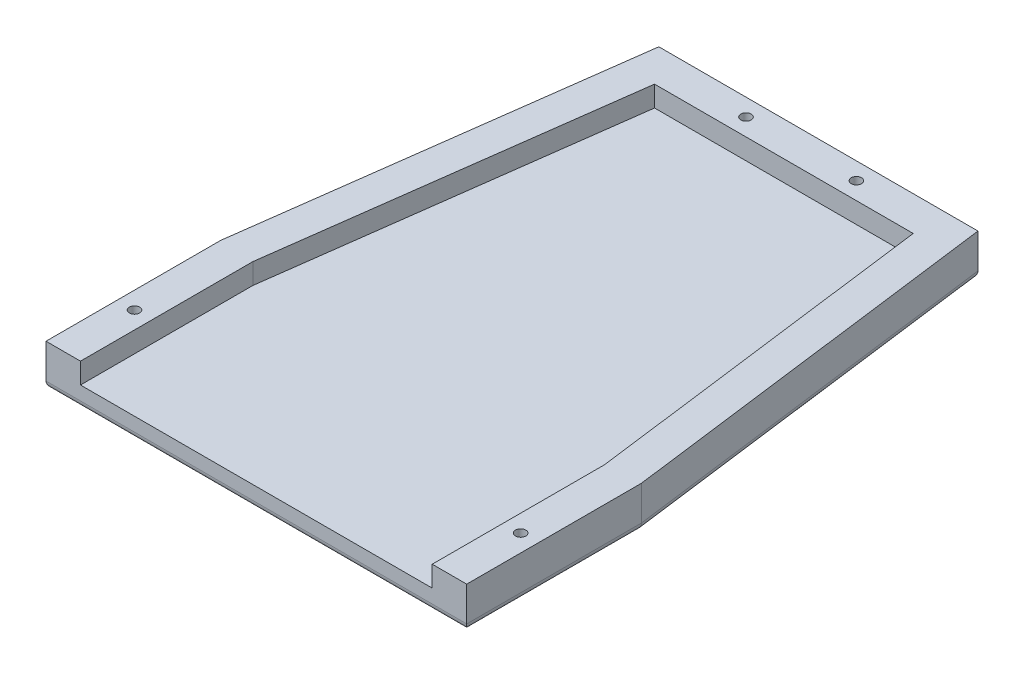
SolidWorks part; units mm, degrees
ref_plane "Płaszczyzna przednia" through (0, 0, 0) normal (0, 0, 1) x (1, 0, 0)
ref_plane "Płaszczyzna górna" through (0, 0, 0) normal (0, 1, 0) x (1, 0, 0)
ref_plane "Płaszczyzna prawa" through (0, 0, 0) normal (1, 0, 0) x (0, 0, -1)
sketch "Szkic1" plane through (0, 0, 0) normal (0, 1, 0) x (1, 0, 0)
  line L0 (-46.2252, 44.9878) -> (-0.2252, 44.9878)
  line L1 (-0.2252, 44.9878) -> (7.2748, -12.8855)
  line L2 (7.2748, -12.8855) -> (7.2748, -36.4122)
  line L3 (7.2748, -36.4122) -> (-53.7252, -36.4122)
  line L4 (-53.7252, -36.4122) -> (-53.7252, -11.4122)
  line L5 (-53.7252, -11.4122) -> (-46.2252, 44.9878)
  dimension "D1" = 46
  dimension "D2" = 61
  dimension "D3" = 7.5
  dimension "D4" = 56.4
  dimension "D5" = 25
  dimension "D6" = 7.5
extrude "Dodanie-wyciągnięcie1" add sketch "Szkic1" along normal blind 3
sketch "Szkic3" plane through (0, 0, 0) normal (0, 1, 0) x (1, 0, 0)
  line L0 (-48.7252, -31.4122) -> (2.2748, -31.4122)
  line L1 (-53.7252, -11.4122) -> (-53.7252, -36.4122) construction
  line L2 (7.2748, -36.4122) -> (7.2748, -12.8855) construction
  line L3 (-48.7252, -31.4122) -> (-48.7252, -11.4122)
  line L4 (-53.7252, -36.4122) -> (7.2748, -36.4122) construction
  line L5 (-41.8901, 39.9878) -> (-4.3863, 39.9878)
  line L6 (-0.2252, 44.9878) -> (-46.2252, 44.9878) construction
  line L7 (-4.3863, 39.9878) -> (2.2748, -11.4122)
  line L8 (-48.7252, -11.4122) -> (-41.8901, 39.9878)
  line L9 (2.2748, -31.4122) -> (2.2748, -11.4122)
  line L10 (-46.2252, 44.9878) -> (-53.7252, -11.4122) construction
  line L11 (7.2748, -12.8855) -> (-0.2252, 44.9878) construction
  dimension "D1" = 51
  dimension "D2" = 5
  dimension "D3" = 5
  dimension "D4" = 5
  dimension "D5" = 20
  dimension "D6" = 5
  dimension "D7" = 0
  dimension "D8" = 0
  dimension "D9" = 20
extrude "Wyciągnięcie-cienka ścianka1" add sketch "Szkic3" along normal blind 6 from offset 0 thin contours L7 L9 L0 L3 L8 L5 thin type one direction wall 5
sketch "Szkic5" plane through (0, 6, 0) normal (0, 1, 0) x (1, 0, 0)
  line L0 (-46.2692, 44.9878) -> (0.0075, 44.9878) construction
  line L1 (7.2748, -36.4122) -> (7.2748, -11.0896) construction
  line L2 (-53.7252, -36.4122) -> (-53.7252, -11.0812) construction
  circle A0 centre (-31.1292, 42.4878) radius 0.75
  circle A1 centre (-15.1292, 42.4878) radius 0.75
  circle A2 centre (-51.2252, -26.0812) radius 0.75
  circle A3 centre (4.7748, -26.0896) radius 0.75
  dimension "D3" = 1.5
  dimension "D4" = 1.5
  dimension "D8" = 1.5
  dimension "D9" = 1.5
  dimension "D1" = 2.5
  dimension "D2" = 2.5
  dimension "D5" = 16
  dimension "D6" = 15.14
  dimension "D7" = 15.1368
  dimension "D10" = 2.5
  dimension "D11" = 2.5
  dimension "D12" = 15
  dimension "D13" = 15
  dimension "D14" = 10.7609
  dimension "D15" = 10.7429
extrude "Wytnij-wyciągnięcie1" cut sketch "Szkic5" against normal blind 39 and the other way blind 51
fillet "Zaokrąglenie1" radius 1 10 edges at (-23.1308, 0, -44.9878) (-49.9972, 0, -16.9533) (-53.7252, 0, 23.7467) (-23.2252, 0, 36.4122) (7.2748, 0, 23.7509) (3.6412, 0, -16.9491) (-31.1292, 0, -43.2378) (-15.1292, 0, -43.2378) (4.7748, 0, 25.3396) (-51.2252, 0, 25.3312)
sketch "Szkic6" plane through (0, 6, 0) normal (0, 1, 0) x (1, 0, 0)
  line L0 (-48.7252, -31.4122) -> (-48.7252, -36.4122)
  line L1 (-53.7252, -36.4122) -> (7.2748, -36.4122) construction
  line L2 (2.2748, -31.4122) -> (2.2748, -36.4122)
  line L3 (2.2748, -36.4122) -> (-48.7252, -36.4122)
  line M8 (2.2748, -31.4122) -> (-48.7252, -31.4122)
  line M14 (-53.7252, -36.4122) -> (7.2748, -36.4122)
extrude "Wytnij-wyciągnięcie2" cut sketch "Szkic6" against normal blind 3 contours L2 L0 M8 M14 region at (-23.2252, 6, 33.9122)
